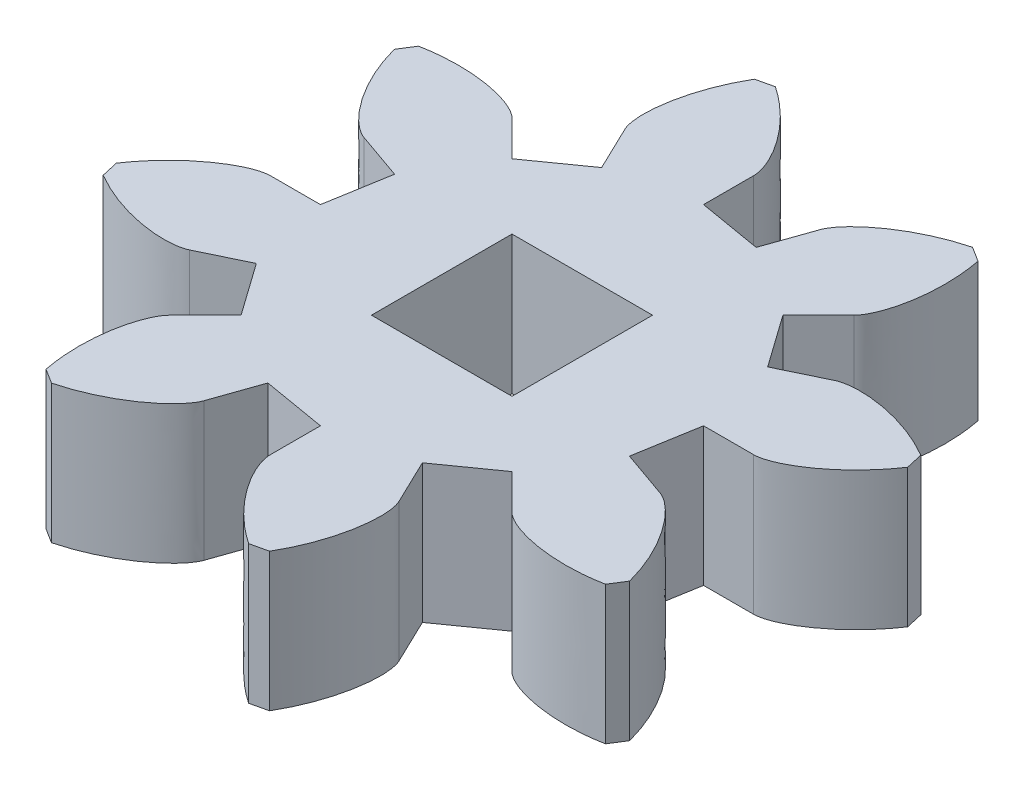
SolidWorks part; units mm, degrees
ref_plane "Front Plane" through (0, 0, 0) normal (0, 0, 1) x (1, 0, 0)
ref_plane "Top Plane" through (0, 0, 0) normal (0, 1, 0) x (1, 0, 0)
ref_plane "Right Plane" through (0, 0, 0) normal (1, 0, 0) x (0, 0, -1)
sketch "Sketch2" plane through (0, 0, 0) normal (0, 1, 0) x (1, 0, 0)
  circle A0 centre (0, 0) radius 5.8346 construction
  circle A1 centre (0, 0) radius 5.8346
sketch "Sketch3" plane through (0, 0, 0) normal (0, 1, 0) x (1, 0, 0)
  line L0 (4.157, 0) -> (5.2447, 0)
  line L1 (5.2447, 0) -> (5.2537, 0.0004)
  line L2 (5.2537, 0.0004) -> (5.2726, 0.002)
  line L3 (5.2726, 0.002) -> (5.3013, 0.0057)
  line L4 (5.3013, 0.0057) -> (5.3397, 0.0123)
  line L5 (5.3397, 0.0123) -> (5.3875, 0.0227)
  line L6 (5.3875, 0.0227) -> (5.4444, 0.0378)
  line L7 (5.4444, 0.0378) -> (5.5102, 0.0582)
  line L8 (5.5102, 0.0582) -> (5.5844, 0.0849)
  line L9 (5.5844, 0.0849) -> (5.6666, 0.1186)
  line L10 (5.6666, 0.1186) -> (5.7563, 0.16)
  line L11 (5.7563, 0.16) -> (5.8531, 0.2099)
  line L12 (5.8531, 0.2099) -> (5.9562, 0.2688)
  line L13 (5.9562, 0.2688) -> (6.0651, 0.3376)
  line L14 (6.0651, 0.3376) -> (6.1791, 0.4167)
  line L15 (6.1791, 0.4167) -> (6.2974, 0.5068)
  line L16 (6.2974, 0.5068) -> (6.4195, 0.6083)
  line L17 (6.4195, 0.6083) -> (6.5443, 0.7218)
  line L18 (6.5443, 0.7218) -> (6.6712, 0.8476)
  line L19 (6.6712, 0.8476) -> (6.7992, 0.9862)
  line L20 (6.7992, 0.9862) -> (6.9276, 1.1378)
  line L21 (6.9276, 1.1378) -> (7.0553, 1.3028)
  line L22 (7.0553, 1.3028) -> (7.1186, 1.3904)
  line L23 (7.1186, 1.3904) -> (7.1501, 1.4354)
  line L24 (7.1501, 1.4354) -> (7.1502, 1.4358)
  line L25 (7.1502, 1.4358) -> (7.0661, 1.8051)
  line L26 (7.0661, 1.8051) -> (7.0658, 1.8053)
  line L27 (7.0658, 1.8053) -> (7.0179, 1.8323)
  line L28 (7.0179, 1.8323) -> (6.9228, 1.8838)
  line L29 (6.9228, 1.8838) -> (6.7362, 1.9771)
  line L30 (6.7362, 1.9771) -> (6.5549, 2.0582)
  line L31 (6.5549, 2.0582) -> (6.3794, 2.1275)
  line L32 (6.3794, 2.1275) -> (6.2105, 2.1859)
  line L33 (6.2105, 2.1859) -> (6.0488, 2.2341)
  line L34 (6.0488, 2.2341) -> (5.8949, 2.2727)
  line L35 (5.8949, 2.2727) -> (5.7492, 2.3025)
  line L36 (5.7492, 2.3025) -> (5.6121, 2.3244)
  line L37 (5.6121, 2.3244) -> (5.4842, 2.3392)
  line L38 (5.4842, 2.3392) -> (5.3657, 2.3477)
  line L39 (5.3657, 2.3477) -> (5.2569, 2.3507)
  line L40 (5.2569, 2.3507) -> (5.1581, 2.3491)
  line L41 (5.1581, 2.3491) -> (5.0694, 2.3438)
  line L42 (5.0694, 2.3438) -> (4.991, 2.3357)
  line L43 (4.991, 2.3357) -> (4.9228, 2.3256)
  line L44 (4.9228, 2.3256) -> (4.865, 2.3145)
  line L45 (4.865, 2.3145) -> (4.8174, 2.3032)
  line L46 (4.8174, 2.3032) -> (4.78, 2.2925)
  line L47 (4.78, 2.2925) -> (4.7525, 2.2834)
  line L48 (4.7525, 2.2834) -> (4.7348, 2.2767)
  line L49 (4.7348, 2.2767) -> (4.7265, 2.2731)
  line L50 (4.7265, 2.2731) -> (3.7463, 1.8017)
  line L51 (3.7463, 1.8017) -> (2.9394, 2.9394)
  line L52 (2.9394, 2.9394) -> (3.7086, 3.7086)
  line L53 (3.7086, 3.7086) -> (3.7146, 3.7152)
  line L54 (3.7146, 3.7152) -> (3.7269, 3.7297)
  line L55 (3.7269, 3.7297) -> (3.7446, 3.7526)
  line L56 (3.7446, 3.7526) -> (3.767, 3.7844)
  line L57 (3.767, 3.7844) -> (3.7934, 3.8256)
  line L58 (3.7934, 3.8256) -> (3.8231, 3.8765)
  line L59 (3.8231, 3.8765) -> (3.8551, 3.9375)
  line L60 (3.8551, 3.9375) -> (3.8887, 4.0088)
  line L61 (3.8887, 4.0088) -> (3.923, 4.0908)
  line L62 (3.923, 4.0908) -> (3.9572, 4.1835)
  line L63 (3.9572, 4.1835) -> (3.9904, 4.2871)
  line L64 (3.9904, 4.2871) -> (4.0216, 4.4018)
  line L65 (4.0216, 4.4018) -> (4.05, 4.5274)
  line L66 (4.05, 4.5274) -> (4.0746, 4.6639)
  line L67 (4.0746, 4.6639) -> (4.0946, 4.8113)
  line L68 (4.0946, 4.8113) -> (4.1091, 4.9694)
  line L69 (4.1091, 4.9694) -> (4.1172, 5.1379)
  line L70 (4.1172, 5.1379) -> (4.1179, 5.3166)
  line L71 (4.1179, 5.3166) -> (4.1105, 5.5051)
  line L72 (4.1105, 5.5051) -> (4.094, 5.7031)
  line L73 (4.094, 5.7031) -> (4.0676, 5.9101)
  line L74 (4.0676, 5.9101) -> (4.0505, 6.0168)
  line L75 (4.0505, 6.0168) -> (4.0409, 6.0709)
  line L76 (4.0409, 6.0709) -> (4.0407, 6.0712)
  line L77 (4.0407, 6.0712) -> (3.7201, 6.2728)
  line L78 (3.7201, 6.2728) -> (3.7197, 6.2728)
  line L79 (3.7197, 6.2728) -> (3.6668, 6.258)
  line L80 (3.6668, 6.258) -> (3.5632, 6.2272)
  line L81 (3.5632, 6.2272) -> (3.3652, 6.1613)
  line L82 (3.3652, 6.1613) -> (3.1797, 6.0903)
  line L83 (3.1797, 6.0903) -> (3.0065, 6.0153)
  line L84 (3.0065, 6.0153) -> (2.8458, 5.9372)
  line L85 (2.8458, 5.9372) -> (2.6974, 5.8569)
  line L86 (2.6974, 5.8569) -> (2.5613, 5.7753)
  line L87 (2.5613, 5.7753) -> (2.4371, 5.6934)
  line L88 (2.4371, 5.6934) -> (2.3247, 5.612)
  line L89 (2.3247, 5.612) -> (2.2238, 5.532)
  line L90 (2.2238, 5.532) -> (2.1341, 5.4542)
  line L91 (2.1341, 5.4542) -> (2.055, 5.3794)
  line L92 (2.055, 5.3794) -> (1.9863, 5.3084)
  line L93 (1.9863, 5.3084) -> (1.9273, 5.242)
  line L94 (1.9273, 5.242) -> (1.8776, 5.1807)
  line L95 (1.8776, 5.1807) -> (1.8365, 5.1254)
  line L96 (1.8365, 5.1254) -> (1.8035, 5.0767)
  line L97 (1.8035, 5.0767) -> (1.7778, 5.035)
  line L98 (1.7778, 5.035) -> (1.7589, 5.001)
  line L99 (1.7589, 5.001) -> (1.7459, 4.9751)
  line L100 (1.7459, 4.9751) -> (1.7382, 4.9578)
  line L101 (1.7382, 4.9578) -> (1.7348, 4.9495)
  line L102 (1.7348, 4.9495) -> (1.375, 3.923)
  line L103 (1.375, 3.923) -> (0, 4.157)
  line L104 (0, 4.157) -> (0, 5.2447)
  line L105 (0, 5.2447) -> (-0.0004, 5.2537)
  line L106 (-0.0004, 5.2537) -> (-0.002, 5.2726)
  line L107 (-0.002, 5.2726) -> (-0.0057, 5.3013)
  line L108 (-0.0057, 5.3013) -> (-0.0123, 5.3397)
  line L109 (-0.0123, 5.3397) -> (-0.0227, 5.3875)
  line L110 (-0.0227, 5.3875) -> (-0.0378, 5.4444)
  line L111 (-0.0378, 5.4444) -> (-0.0582, 5.5102)
  line L112 (-0.0582, 5.5102) -> (-0.0849, 5.5844)
  line L113 (-0.0849, 5.5844) -> (-0.1186, 5.6666)
  line L114 (-0.1186, 5.6666) -> (-0.16, 5.7563)
  line L115 (-0.16, 5.7563) -> (-0.2099, 5.8531)
  line L116 (-0.2099, 5.8531) -> (-0.2688, 5.9562)
  line L117 (-0.2688, 5.9562) -> (-0.3376, 6.0651)
  line L118 (-0.3376, 6.0651) -> (-0.4167, 6.1791)
  line L119 (-0.4167, 6.1791) -> (-0.5068, 6.2974)
  line L120 (-0.5068, 6.2974) -> (-0.6083, 6.4195)
  line L121 (-0.6083, 6.4195) -> (-0.7218, 6.5443)
  line L122 (-0.7218, 6.5443) -> (-0.8476, 6.6712)
  line L123 (-0.8476, 6.6712) -> (-0.9862, 6.7992)
  line L124 (-0.9862, 6.7992) -> (-1.1378, 6.9276)
  line L125 (-1.1378, 6.9276) -> (-1.3028, 7.0553)
  line L126 (-1.3028, 7.0553) -> (-1.3904, 7.1186)
  line L127 (-1.3904, 7.1186) -> (-1.4354, 7.1501)
  line L128 (-1.4354, 7.1501) -> (-1.4358, 7.1502)
  line L129 (-1.4358, 7.1502) -> (-1.8051, 7.0661)
  line L130 (-1.8051, 7.0661) -> (-1.8053, 7.0658)
  line L131 (-1.8053, 7.0658) -> (-1.8323, 7.0179)
  line L132 (-1.8323, 7.0179) -> (-1.8838, 6.9228)
  line L133 (-1.8838, 6.9228) -> (-1.9771, 6.7362)
  line L134 (-1.9771, 6.7362) -> (-2.0582, 6.5549)
  line L135 (-2.0582, 6.5549) -> (-2.1275, 6.3794)
  line L136 (-2.1275, 6.3794) -> (-2.1859, 6.2105)
  line L137 (-2.1859, 6.2105) -> (-2.2341, 6.0488)
  line L138 (-2.2341, 6.0488) -> (-2.2727, 5.8949)
  line L139 (-2.2727, 5.8949) -> (-2.3025, 5.7492)
  line L140 (-2.3025, 5.7492) -> (-2.3244, 5.6121)
  line L141 (-2.3244, 5.6121) -> (-2.3392, 5.4842)
  line L142 (-2.3392, 5.4842) -> (-2.3477, 5.3657)
  line L143 (-2.3477, 5.3657) -> (-2.3507, 5.2569)
  line L144 (-2.3507, 5.2569) -> (-2.3491, 5.1581)
  line L145 (-2.3491, 5.1581) -> (-2.3438, 5.0694)
  line L146 (-2.3438, 5.0694) -> (-2.3357, 4.991)
  line L147 (-2.3357, 4.991) -> (-2.3256, 4.9228)
  line L148 (-2.3256, 4.9228) -> (-2.3145, 4.865)
  line L149 (-2.3145, 4.865) -> (-2.3032, 4.8174)
  line L150 (-2.3032, 4.8174) -> (-2.2925, 4.78)
  line L151 (-2.2925, 4.78) -> (-2.2834, 4.7525)
  line L152 (-2.2834, 4.7525) -> (-2.2767, 4.7348)
  line L153 (-2.2767, 4.7348) -> (-2.2731, 4.7265)
  line L154 (-2.2731, 4.7265) -> (-1.8017, 3.7463)
  line L155 (-1.8017, 3.7463) -> (-2.9394, 2.9394)
  line L156 (-2.9394, 2.9394) -> (-3.7086, 3.7086)
  line L157 (-3.7086, 3.7086) -> (-3.7152, 3.7146)
  line L158 (-3.7152, 3.7146) -> (-3.7297, 3.7269)
  line L159 (-3.7297, 3.7269) -> (-3.7526, 3.7446)
  line L160 (-3.7526, 3.7446) -> (-3.7844, 3.767)
  line L161 (-3.7844, 3.767) -> (-3.8256, 3.7934)
  line L162 (-3.8256, 3.7934) -> (-3.8765, 3.8231)
  line L163 (-3.8765, 3.8231) -> (-3.9375, 3.8551)
  line L164 (-3.9375, 3.8551) -> (-4.0088, 3.8887)
  line L165 (-4.0088, 3.8887) -> (-4.0908, 3.923)
  line L166 (-4.0908, 3.923) -> (-4.1835, 3.9572)
  line L167 (-4.1835, 3.9572) -> (-4.2871, 3.9904)
  line L168 (-4.2871, 3.9904) -> (-4.4018, 4.0216)
  line L169 (-4.4018, 4.0216) -> (-4.5274, 4.05)
  line L170 (-4.5274, 4.05) -> (-4.6639, 4.0746)
  line L171 (-4.6639, 4.0746) -> (-4.8113, 4.0946)
  line L172 (-4.8113, 4.0946) -> (-4.9694, 4.1091)
  line L173 (-4.9694, 4.1091) -> (-5.1379, 4.1172)
  line L174 (-5.1379, 4.1172) -> (-5.3166, 4.1179)
  line L175 (-5.3166, 4.1179) -> (-5.5051, 4.1105)
  line L176 (-5.5051, 4.1105) -> (-5.7031, 4.094)
  line L177 (-5.7031, 4.094) -> (-5.9101, 4.0676)
  line L178 (-5.9101, 4.0676) -> (-6.0168, 4.0505)
  line L179 (-6.0168, 4.0505) -> (-6.0709, 4.0409)
  line L180 (-6.0709, 4.0409) -> (-6.0712, 4.0407)
  line L181 (-6.0712, 4.0407) -> (-6.2728, 3.7201)
  line L182 (-6.2728, 3.7201) -> (-6.2728, 3.7197)
  line L183 (-6.2728, 3.7197) -> (-6.258, 3.6668)
  line L184 (-6.258, 3.6668) -> (-6.2272, 3.5632)
  line L185 (-6.2272, 3.5632) -> (-6.1613, 3.3652)
  line L186 (-6.1613, 3.3652) -> (-6.0903, 3.1797)
  line L187 (-6.0903, 3.1797) -> (-6.0153, 3.0065)
  line L188 (-6.0153, 3.0065) -> (-5.9372, 2.8458)
  line L189 (-5.9372, 2.8458) -> (-5.8569, 2.6974)
  line L190 (-5.8569, 2.6974) -> (-5.7753, 2.5613)
  line L191 (-5.7753, 2.5613) -> (-5.6934, 2.4371)
  line L192 (-5.6934, 2.4371) -> (-5.612, 2.3247)
  line L193 (-5.612, 2.3247) -> (-5.532, 2.2238)
  line L194 (-5.532, 2.2238) -> (-5.4542, 2.1341)
  line L195 (-5.4542, 2.1341) -> (-5.3794, 2.055)
  line L196 (-5.3794, 2.055) -> (-5.3084, 1.9863)
  line L197 (-5.3084, 1.9863) -> (-5.242, 1.9273)
  line L198 (-5.242, 1.9273) -> (-5.1807, 1.8776)
  line L199 (-5.1807, 1.8776) -> (-5.1254, 1.8365)
  line L200 (-5.1254, 1.8365) -> (-5.0767, 1.8035)
  line L201 (-5.0767, 1.8035) -> (-5.035, 1.7778)
  line L202 (-5.035, 1.7778) -> (-5.001, 1.7589)
  line L203 (-5.001, 1.7589) -> (-4.9751, 1.7459)
  line L204 (-4.9751, 1.7459) -> (-4.9578, 1.7382)
  line L205 (-4.9578, 1.7382) -> (-4.9495, 1.7348)
  line L206 (-4.9495, 1.7348) -> (-3.923, 1.375)
  line L207 (-3.923, 1.375) -> (-4.157, 0)
  line L208 (-4.157, 0) -> (-5.2447, 0)
  line L209 (-5.2447, 0) -> (-5.2537, -0.0004)
  line L210 (-5.2537, -0.0004) -> (-5.2726, -0.002)
  line L211 (-5.2726, -0.002) -> (-5.3013, -0.0057)
  line L212 (-5.3013, -0.0057) -> (-5.3397, -0.0123)
  line L213 (-5.3397, -0.0123) -> (-5.3875, -0.0227)
  line L214 (-5.3875, -0.0227) -> (-5.4444, -0.0378)
  line L215 (-5.4444, -0.0378) -> (-5.5102, -0.0582)
  line L216 (-5.5102, -0.0582) -> (-5.5844, -0.0849)
  line L217 (-5.5844, -0.0849) -> (-5.6666, -0.1186)
  line L218 (-5.6666, -0.1186) -> (-5.7563, -0.16)
  line L219 (-5.7563, -0.16) -> (-5.8531, -0.2099)
  line L220 (-5.8531, -0.2099) -> (-5.9562, -0.2688)
  line L221 (-5.9562, -0.2688) -> (-6.0651, -0.3376)
  line L222 (-6.0651, -0.3376) -> (-6.1791, -0.4167)
  line L223 (-6.1791, -0.4167) -> (-6.2974, -0.5068)
  line L224 (-6.2974, -0.5068) -> (-6.4195, -0.6083)
  line L225 (-6.4195, -0.6083) -> (-6.5443, -0.7218)
  line L226 (-6.5443, -0.7218) -> (-6.6712, -0.8476)
  line L227 (-6.6712, -0.8476) -> (-6.7992, -0.9862)
  line L228 (-6.7992, -0.9862) -> (-6.9276, -1.1378)
  line L229 (-6.9276, -1.1378) -> (-7.0553, -1.3028)
  line L230 (-7.0553, -1.3028) -> (-7.1186, -1.3904)
  line L231 (-7.1186, -1.3904) -> (-7.1501, -1.4354)
  line L232 (-7.1501, -1.4354) -> (-7.1502, -1.4358)
  line L233 (-7.1502, -1.4358) -> (-7.0661, -1.8051)
  line L234 (-7.0661, -1.8051) -> (-7.0658, -1.8053)
  line L235 (-7.0658, -1.8053) -> (-7.0179, -1.8323)
  line L236 (-7.0179, -1.8323) -> (-6.9228, -1.8838)
  line L237 (-6.9228, -1.8838) -> (-6.7362, -1.9771)
  line L238 (-6.7362, -1.9771) -> (-6.5549, -2.0582)
  line L239 (-6.5549, -2.0582) -> (-6.3794, -2.1275)
  line L240 (-6.3794, -2.1275) -> (-6.2105, -2.1859)
  line L241 (-6.2105, -2.1859) -> (-6.0488, -2.2341)
  line L242 (-6.0488, -2.2341) -> (-5.8949, -2.2727)
  line L243 (-5.8949, -2.2727) -> (-5.7492, -2.3025)
  line L244 (-5.7492, -2.3025) -> (-5.6121, -2.3244)
  line L245 (-5.6121, -2.3244) -> (-5.4842, -2.3392)
  line L246 (-5.4842, -2.3392) -> (-5.3657, -2.3477)
  line L247 (-5.3657, -2.3477) -> (-5.2569, -2.3507)
  line L248 (-5.2569, -2.3507) -> (-5.1581, -2.3491)
  line L249 (-5.1581, -2.3491) -> (-5.0694, -2.3438)
  line L250 (-5.0694, -2.3438) -> (-4.991, -2.3357)
  line L251 (-4.991, -2.3357) -> (-4.9228, -2.3256)
  line L252 (-4.9228, -2.3256) -> (-4.865, -2.3145)
  line L253 (-4.865, -2.3145) -> (-4.8174, -2.3032)
  line L254 (-4.8174, -2.3032) -> (-4.78, -2.2925)
  line L255 (-4.78, -2.2925) -> (-4.7525, -2.2834)
  line L256 (-4.7525, -2.2834) -> (-4.7348, -2.2767)
  line L257 (-4.7348, -2.2767) -> (-4.7265, -2.2731)
  line L258 (-4.7265, -2.2731) -> (-3.7463, -1.8017)
  line L259 (-3.7463, -1.8017) -> (-2.9394, -2.9394)
  line L260 (-2.9394, -2.9394) -> (-3.7086, -3.7086)
  line L261 (-3.7086, -3.7086) -> (-3.7146, -3.7152)
  line L262 (-3.7146, -3.7152) -> (-3.7269, -3.7297)
  line L263 (-3.7269, -3.7297) -> (-3.7446, -3.7526)
  line L264 (-3.7446, -3.7526) -> (-3.767, -3.7844)
  line L265 (-3.767, -3.7844) -> (-3.7934, -3.8256)
  line L266 (-3.7934, -3.8256) -> (-3.8231, -3.8765)
  line L267 (-3.8231, -3.8765) -> (-3.8551, -3.9375)
  line L268 (-3.8551, -3.9375) -> (-3.8887, -4.0088)
  line L269 (-3.8887, -4.0088) -> (-3.923, -4.0908)
  line L270 (-3.923, -4.0908) -> (-3.9572, -4.1835)
  line L271 (-3.9572, -4.1835) -> (-3.9904, -4.2871)
  line L272 (-3.9904, -4.2871) -> (-4.0216, -4.4018)
  line L273 (-4.0216, -4.4018) -> (-4.05, -4.5274)
  line L274 (-4.05, -4.5274) -> (-4.0746, -4.6639)
  line L275 (-4.0746, -4.6639) -> (-4.0946, -4.8113)
  line L276 (-4.0946, -4.8113) -> (-4.1091, -4.9694)
  line L277 (-4.1091, -4.9694) -> (-4.1172, -5.1379)
  line L278 (-4.1172, -5.1379) -> (-4.1179, -5.3166)
  line L279 (-4.1179, -5.3166) -> (-4.1105, -5.5051)
  line L280 (-4.1105, -5.5051) -> (-4.094, -5.7031)
  line L281 (-4.094, -5.7031) -> (-4.0676, -5.9101)
  line L282 (-4.0676, -5.9101) -> (-4.0505, -6.0168)
  line L283 (-4.0505, -6.0168) -> (-4.0409, -6.0709)
  line L284 (-4.0409, -6.0709) -> (-4.0407, -6.0712)
  line L285 (-4.0407, -6.0712) -> (-3.7201, -6.2728)
  line L286 (-3.7201, -6.2728) -> (-3.7197, -6.2728)
  line L287 (-3.7197, -6.2728) -> (-3.6668, -6.258)
  line L288 (-3.6668, -6.258) -> (-3.5632, -6.2272)
  line L289 (-3.5632, -6.2272) -> (-3.3652, -6.1613)
  line L290 (-3.3652, -6.1613) -> (-3.1797, -6.0903)
  line L291 (-3.1797, -6.0903) -> (-3.0065, -6.0153)
  line L292 (-3.0065, -6.0153) -> (-2.8458, -5.9372)
  line L293 (-2.8458, -5.9372) -> (-2.6974, -5.8569)
  line L294 (-2.6974, -5.8569) -> (-2.5613, -5.7753)
  line L295 (-2.5613, -5.7753) -> (-2.4371, -5.6934)
  line L296 (-2.4371, -5.6934) -> (-2.3247, -5.612)
  line L297 (-2.3247, -5.612) -> (-2.2238, -5.532)
  line L298 (-2.2238, -5.532) -> (-2.1341, -5.4542)
  line L299 (-2.1341, -5.4542) -> (-2.055, -5.3794)
  line L300 (-2.055, -5.3794) -> (-1.9863, -5.3084)
  line L301 (-1.9863, -5.3084) -> (-1.9273, -5.242)
  line L302 (-1.9273, -5.242) -> (-1.8776, -5.1807)
  line L303 (-1.8776, -5.1807) -> (-1.8365, -5.1254)
  line L304 (-1.8365, -5.1254) -> (-1.8035, -5.0767)
  line L305 (-1.8035, -5.0767) -> (-1.7778, -5.035)
  line L306 (-1.7778, -5.035) -> (-1.7589, -5.001)
  line L307 (-1.7589, -5.001) -> (-1.7459, -4.9751)
  line L308 (-1.7459, -4.9751) -> (-1.7382, -4.9578)
  line L309 (-1.7382, -4.9578) -> (-1.7348, -4.9495)
  line L310 (-1.7348, -4.9495) -> (-1.375, -3.923)
  line L311 (-1.375, -3.923) -> (0, -4.157)
  line L312 (0, -4.157) -> (0, -5.2447)
  line L313 (0, -5.2447) -> (0.0004, -5.2537)
  line L314 (0.0004, -5.2537) -> (0.002, -5.2726)
  line L315 (0.002, -5.2726) -> (0.0057, -5.3013)
  line L316 (0.0057, -5.3013) -> (0.0123, -5.3397)
  line L317 (0.0123, -5.3397) -> (0.0227, -5.3875)
  line L318 (0.0227, -5.3875) -> (0.0378, -5.4444)
  line L319 (0.0378, -5.4444) -> (0.0582, -5.5102)
  line L320 (0.0582, -5.5102) -> (0.0849, -5.5844)
  line L321 (0.0849, -5.5844) -> (0.1186, -5.6666)
  line L322 (0.1186, -5.6666) -> (0.16, -5.7563)
  line L323 (0.16, -5.7563) -> (0.2099, -5.8531)
  line L324 (0.2099, -5.8531) -> (0.2688, -5.9562)
  line L325 (0.2688, -5.9562) -> (0.3376, -6.0651)
  line L326 (0.3376, -6.0651) -> (0.4167, -6.1791)
  line L327 (0.4167, -6.1791) -> (0.5068, -6.2974)
  line L328 (0.5068, -6.2974) -> (0.6083, -6.4195)
  line L329 (0.6083, -6.4195) -> (0.7218, -6.5443)
  line L330 (0.7218, -6.5443) -> (0.8476, -6.6712)
  line L331 (0.8476, -6.6712) -> (0.9862, -6.7992)
  line L332 (0.9862, -6.7992) -> (1.1378, -6.9276)
  line L333 (1.1378, -6.9276) -> (1.3028, -7.0553)
  line L334 (1.3028, -7.0553) -> (1.3904, -7.1186)
  line L335 (1.3904, -7.1186) -> (1.4354, -7.1501)
  line L336 (1.4354, -7.1501) -> (1.4358, -7.1502)
  line L337 (1.4358, -7.1502) -> (1.8051, -7.0661)
  line L338 (1.8051, -7.0661) -> (1.8053, -7.0658)
  line L339 (1.8053, -7.0658) -> (1.8323, -7.0179)
  line L340 (1.8323, -7.0179) -> (1.8838, -6.9228)
  line L341 (1.8838, -6.9228) -> (1.9771, -6.7362)
  line L342 (1.9771, -6.7362) -> (2.0582, -6.5549)
  line L343 (2.0582, -6.5549) -> (2.1275, -6.3794)
  line L344 (2.1275, -6.3794) -> (2.1859, -6.2105)
  line L345 (2.1859, -6.2105) -> (2.2341, -6.0488)
  line L346 (2.2341, -6.0488) -> (2.2727, -5.8949)
  line L347 (2.2727, -5.8949) -> (2.3025, -5.7492)
  line L348 (2.3025, -5.7492) -> (2.3244, -5.6121)
  line L349 (2.3244, -5.6121) -> (2.3392, -5.4842)
  line L350 (2.3392, -5.4842) -> (2.3477, -5.3657)
  line L351 (2.3477, -5.3657) -> (2.3507, -5.2569)
  line L352 (2.3507, -5.2569) -> (2.3491, -5.1581)
  line L353 (2.3491, -5.1581) -> (2.3438, -5.0694)
  line L354 (2.3438, -5.0694) -> (2.3357, -4.991)
  line L355 (2.3357, -4.991) -> (2.3256, -4.9228)
  line L356 (2.3256, -4.9228) -> (2.3145, -4.865)
  line L357 (2.3145, -4.865) -> (2.3032, -4.8174)
  line L358 (2.3032, -4.8174) -> (2.2925, -4.78)
  line L359 (2.2925, -4.78) -> (2.2834, -4.7525)
  line L360 (2.2834, -4.7525) -> (2.2767, -4.7348)
  line L361 (2.2767, -4.7348) -> (2.2731, -4.7265)
  line L362 (2.2731, -4.7265) -> (1.8017, -3.7463)
  line L363 (1.8017, -3.7463) -> (2.9394, -2.9394)
  line L364 (2.9394, -2.9394) -> (3.7086, -3.7086)
  line L365 (3.7086, -3.7086) -> (3.7152, -3.7146)
  line L366 (3.7152, -3.7146) -> (3.7297, -3.7269)
  line L367 (3.7297, -3.7269) -> (3.7526, -3.7446)
  line L368 (3.7526, -3.7446) -> (3.7844, -3.767)
  line L369 (3.7844, -3.767) -> (3.8256, -3.7934)
  line L370 (3.8256, -3.7934) -> (3.8765, -3.8231)
  line L371 (3.8765, -3.8231) -> (3.9375, -3.8551)
  line L372 (3.9375, -3.8551) -> (4.0088, -3.8887)
  line L373 (4.0088, -3.8887) -> (4.0908, -3.923)
  line L374 (4.0908, -3.923) -> (4.1835, -3.9572)
  line L375 (4.1835, -3.9572) -> (4.2871, -3.9904)
  line L376 (4.2871, -3.9904) -> (4.4018, -4.0216)
  line L377 (4.4018, -4.0216) -> (4.5274, -4.05)
  line L378 (4.5274, -4.05) -> (4.6639, -4.0746)
  line L379 (4.6639, -4.0746) -> (4.8113, -4.0946)
  line L380 (4.8113, -4.0946) -> (4.9694, -4.1091)
  line L381 (4.9694, -4.1091) -> (5.1379, -4.1172)
  line L382 (5.1379, -4.1172) -> (5.3166, -4.1179)
  line L383 (5.3166, -4.1179) -> (5.5051, -4.1105)
  line L384 (5.5051, -4.1105) -> (5.7031, -4.094)
  line L385 (5.7031, -4.094) -> (5.9101, -4.0676)
  line L386 (5.9101, -4.0676) -> (6.0168, -4.0505)
  line L387 (6.0168, -4.0505) -> (6.0709, -4.0409)
  line L388 (6.0709, -4.0409) -> (6.0712, -4.0407)
  line L389 (6.0712, -4.0407) -> (6.2728, -3.7201)
  line L390 (6.2728, -3.7201) -> (6.2728, -3.7197)
  line L391 (6.2728, -3.7197) -> (6.258, -3.6668)
  line L392 (6.258, -3.6668) -> (6.2272, -3.5632)
  line L393 (6.2272, -3.5632) -> (6.1613, -3.3652)
  line L394 (6.1613, -3.3652) -> (6.0903, -3.1797)
  line L395 (6.0903, -3.1797) -> (6.0153, -3.0065)
  line L396 (6.0153, -3.0065) -> (5.9372, -2.8458)
  line L397 (5.9372, -2.8458) -> (5.8569, -2.6974)
  line L398 (5.8569, -2.6974) -> (5.7753, -2.5613)
  line L399 (5.7753, -2.5613) -> (5.6934, -2.4371)
  line L400 (5.6934, -2.4371) -> (5.612, -2.3247)
  line L401 (5.612, -2.3247) -> (5.532, -2.2238)
  line L402 (5.532, -2.2238) -> (5.4542, -2.1341)
  line L403 (5.4542, -2.1341) -> (5.3794, -2.055)
  line L404 (5.3794, -2.055) -> (5.3084, -1.9863)
  line L405 (5.3084, -1.9863) -> (5.242, -1.9273)
  line L406 (5.242, -1.9273) -> (5.1807, -1.8776)
  line L407 (5.1807, -1.8776) -> (5.1254, -1.8365)
  line L408 (5.1254, -1.8365) -> (5.0767, -1.8035)
  line L409 (5.0767, -1.8035) -> (5.035, -1.7778)
  line L410 (5.035, -1.7778) -> (5.001, -1.7589)
  line L411 (5.001, -1.7589) -> (4.9751, -1.7459)
  line L412 (4.9751, -1.7459) -> (4.9578, -1.7382)
  line L413 (4.9578, -1.7382) -> (4.9495, -1.7348)
  line L414 (4.9495, -1.7348) -> (3.923, -1.375)
  line L415 (3.923, -1.375) -> (4.157, 0)
  circle A0 centre (5.6884, 1.2968) radius 0.5725 construction
  circle A1 centre (0, 0) radius 5.8344 construction
  circle A2 centre (0, 0) radius 7.293 construction
  circle A3 centre (0, 0) radius 5.2439 construction
sketch "Sketch5" plane through (0, 0, 0) normal (0, 1, 0) x (1, 0, 0)
  line L0 (0, 0) -> (7.1082, 1.6204) construction
  line L1 (7.1502, 1.4358) -> (7.0661, 1.8051) construction
  line L2 (0, 0) -> (3.3429, 2.3706)
  line L3 (3.7463, 1.8017) -> (2.9394, 2.9394) construction
  line L4 (3.3429, 2.3706) -> (3.7463, 1.8017)
  line L5 (3.7463, 1.8017) -> (4.7265, 2.2731)
  line L6 (7.0661, 1.8051) -> (7.1082, 1.6204)
  line L7 (4.157, 0) -> (5.2447, 0)
  line L8 (4.04, -0.6875) -> (4.157, 0)
  line L9 (0, 0) -> (4.04, -0.6875)
  line L10 (7.1502, 1.4358) -> (7.1082, 1.6204)
  spline S0 degree 3 poles (4.7265, 2.2731) (5.0838, 2.445) (6.115, 2.3613) (7.0661, 1.8051) knots 0 0 0 0 1 1 1 1
  spline S1 degree 3 poles (5.2447, 0) (5.6412, 0) (6.5342, 0.5224) (7.1502, 1.4358) knots 0 0 0 0 1 1 1 1
  dimension "D1" = 22.5
extrude "Boss-Extrude1" add sketch "Sketch5" along normal blind 1.5 and the other way blind 1.5
pattern_circular "CirPattern1" count 8 over 360 about axis through (0, -1.5, 0) along (0, 1, 0) of "Boss-Extrude1"
sketch "Sketch4" plane through (0, 1.5, 0) normal (0, 1, 0) x (1, 0, 0)
  line L1 (-1.525, 1.525) -> (1.525, 1.525)
  line L2 (-1.525, 1.525) -> (-1.525, -1.525)
  line L3 (-1.525, -1.525) -> (1.525, -1.525)
  line L4 (1.525, 1.525) -> (1.525, -1.525)
  line L5 (0, -1.525) -> (0, 1.525) construction
  line L6 (-1.525, 0) -> (1.525, 0) construction
  point P0 (0, 0)
  dimension "D1" = 3.05
extrude "Cut-Extrude1" cut sketch "Sketch4" against normal through all
